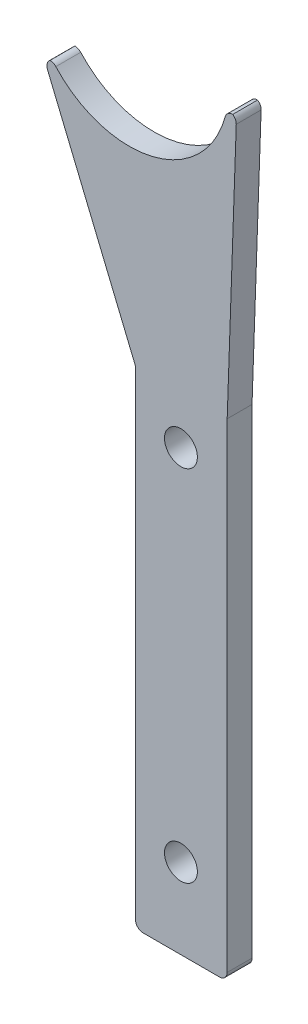
SolidWorks part; units mm, degrees
material "AISI 4130 Steel, annealed at 865C"
ref_plane "X-Y Datum" through (0, 0, 0) normal (0, 0, 1) x (1, 0, 0)
ref_plane "X-Z Datum" through (0, 0, 0) normal (0, 1, 0) x (1, 0, 0)
ref_plane "Y-Z Datum" through (0, 0, 0) normal (1, 0, 0) x (0, 0, -1)
sketch "Sketch1" plane through (0, 0, 0) normal (0, 0, 1) x (1, 0, 0)
  line L5 (7.5537, 70.7143) -> (-1.524, 70.7143)
  line L8 (-1.524, 70.7143) -> (-1.524, 132.9713)
  line L10 (-11.977, 161.3144) -> (-13.247, 161.3144)
  line L11 (7.5537, 70.7143) -> (10.2026, 70.7143)
  line L12 (10.2026, 70.7143) -> (10.2026, 132.9713)
  line L15 (-13.247, 161.3144) -> (-1.524, 132.9713)
  line L17 (11.3925, 167.0067) -> (10.2026, 132.9713)
  line L18 (10.1225, 167.0067) -> (11.3925, 167.0067)
  circle A0 centre (4.2926, 126.8203) radius 2.1
  circle A1 centre (4.2926, 80.9517) radius 2.1
  arc A2 (-11.977, 161.3144) -> (10.1225, 167.0067) centre (-2.3181, 169.5604) ccw
extrude "Boss-Extrude1" add sketch "Sketch1" along normal blind 3.175
fillet "Fillet2" radius 1 5 edges at (10.2026, 70.7143, 1.5875) (-1.524, 70.7143, 1.5875) (-1.524, 132.9713, 1.5875) (10.1225, 167.0067, 1.5875) (-11.977, 161.3144, 1.5875)
fillet "Fillet3" radius 1 2 edges at (-13.247, 161.3144, 1.5875) (11.3925, 167.0067, 1.5875)
